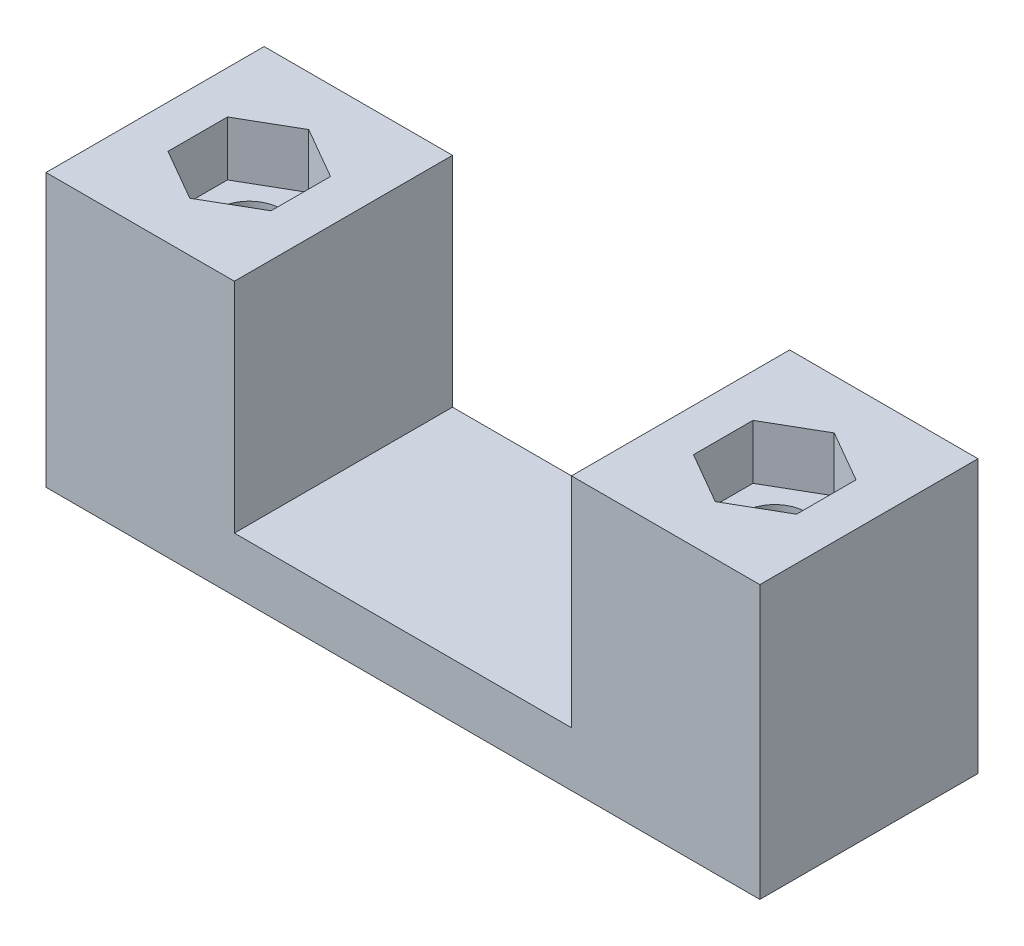
SolidWorks part; units mm, degrees
ref_plane "Front Plane" through (0, 0, 0) normal (0, 0, 1) x (1, 0, 0)
ref_plane "Top Plane" through (0, 0, 0) normal (0, 1, 0) x (1, 0, 0)
ref_plane "Right Plane" through (0, 0, 0) normal (1, 0, 0) x (0, 0, -1)
sketch "Sketch1" plane through (0, 0, 0) normal (0, 1, 0) x (1, 0, 0)
  line L1 (0, 0) -> (72, 0)
  line L2 (0, 0) -> (0, 22)
  line L3 (0, 22) -> (72, 22)
  line L4 (72, 0) -> (72, 22)
  line L7 (30.2143, -18.8036) -> (29.5714, -18.8036)
  dimension "D1" = 72
  dimension "D2" = 22
extrude "Boss-Extrude1" add sketch "Sketch1" along normal blind 27.5 contours L1 L4 L3 L2 region at (36, 0, -11)
sketch "Sketch2" plane through (0, 27.5, 0) normal (0, 1, 0) x (1, 0, 0)
  line L0 (0, 0) -> (72, 0) construction
  line L1 (19, 22) -> (53, 22)
  line L2 (19, 22) -> (19, 0)
  line L3 (19, 0) -> (53, 0)
  line L4 (53, 22) -> (53, 0)
  line L5 (19, 22) -> (53, 0) construction
  line L6 (19, 0) -> (53, 22) construction
  line L7 (36, 0) -> (36, 11) construction
  point P0 (36, 11)
  dimension "D1" = 34
  dimension "D2" = 22
extrude "Cut-Extrude1" cut sketch "Sketch2" against normal blind 22
sketch "Sketch3" plane through (0, 27.5, 0) normal (0, 1, 0) x (1, 0, 0)
  line L0 (36, 22) -> (36, 0) construction
  line L1 (53, 22) -> (19, 22) construction
  line L2 (19, 0) -> (53, 0) construction
  line L3 (19, 22) -> (19, 0) construction
  circle A0 centre (9.5, 11) radius 3.175
  circle A1 centre (62.5, 11) radius 3.175
  dimension "D1" = 6.35
  dimension "D2" = 9.5
extrude "Cut-Extrude2" cut sketch "Sketch3" against normal blind 69
sketch "Sketch4" plane through (0, 27.5, 0) normal (0, 1, 0) x (1, 0, 0)
  line L0 (36, 22) -> (36, 0) construction
  line L1 (9.5, 17) -> (4.3038, 14)
  line L2 (4.3038, 14) -> (4.3038, 8)
  line L3 (4.3038, 8) -> (9.5, 5)
  line L4 (9.5, 5) -> (14.6962, 8)
  line L5 (14.6962, 8) -> (14.6962, 14)
  line L6 (14.6962, 14) -> (9.5, 17)
  line L7 (53, 22) -> (19, 22) construction
  line L8 (19, 0) -> (53, 0) construction
  line L9 (57.3038, 14) -> (62.5, 17)
  line L10 (57.3038, 8) -> (57.3038, 14)
  line L11 (62.5, 5) -> (57.3038, 8)
  line L12 (67.6962, 8) -> (62.5, 5)
  line L13 (67.6962, 14) -> (67.6962, 8)
  line L14 (62.5, 17) -> (67.6962, 14)
  circle A0 centre (9.5, 11) radius 5.1962 construction
  circle A1 centre (62.5, 11) radius 5.1962 construction
  dimension "D1" = 6
extrude "Cut-Extrude3" cut sketch "Sketch4" against normal blind 5.5
